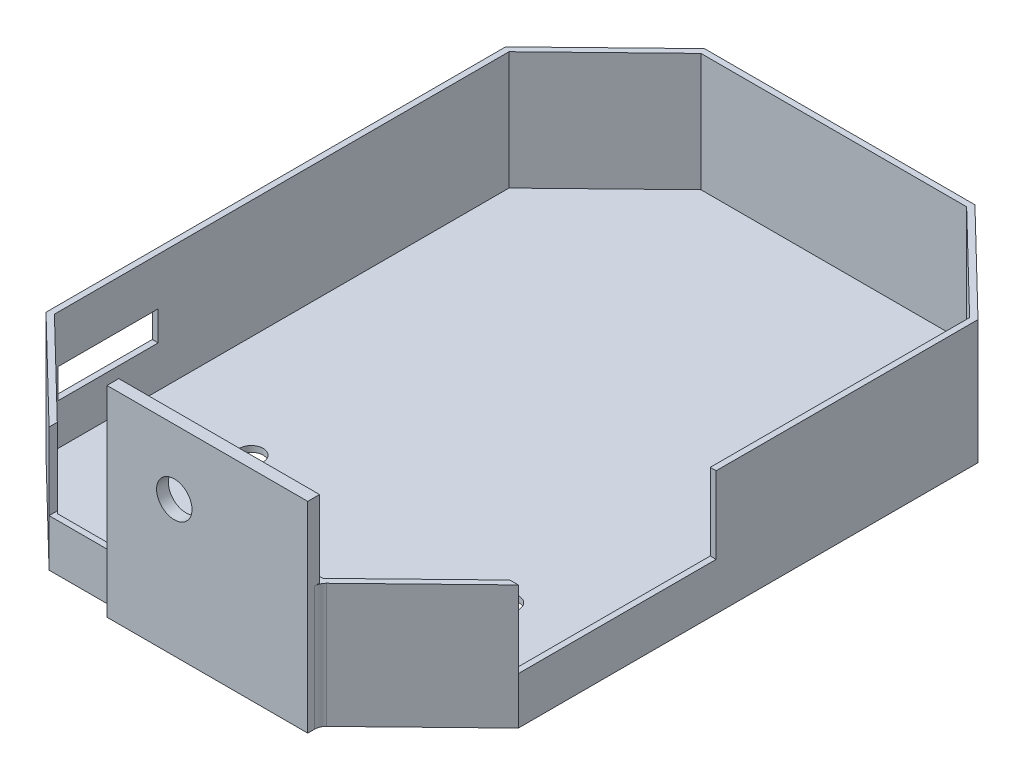
SolidWorks part; units mm, degrees
ref_plane "Alzado" through (0, 0, 0) normal (0, 0, 1) x (1, 0, 0)
ref_plane "Planta" through (0, 0, 0) normal (0, 1, 0) x (1, 0, 0)
ref_plane "Vista lateral" through (0, 0, 0) normal (1, 0, 0) x (0, 0, -1)
sketch "Croquis1" plane through (0, 0, 0) normal (0, 1, 0) x (1, 0, 0)
  line L0 (0, 0) -> (78, 0)
  line L1 (78, 0) -> (78, 109)
  line L2 (78, 109) -> (0, 109)
  line L3 (0, 109) -> (0, 0)
  line L4 (39, 109) -> (39, 0) construction
  line L5 (61.5, 109) -> (78, 93)
  line L6 (0, 54.5) -> (78, 54.5) construction
  line L7 (16.5, 109) -> (0, 93)
  line L8 (61.5, 0) -> (78, 16)
  line L9 (16.5, 0) -> (0, 16)
  dimension "D1" = 78
  dimension "D2" = 109
  dimension "D3" = 22.5
  dimension "D4" = 38.5
extrude "Saliente-Extruir1" add sketch "Croquis1" along normal blind 20 contours L9 L0 L8 L1 L5 L2 L7 L3 region at (39, 0, -54.5)
shell "Vaciado1" thickness 1 removed face at (39, 20, -54.5) outward yes
sketch "Croquis2" plane through (0, 0, 1) normal (0, 0, 1) x (1, 0, 0)
  line L0 (16.0948, 14.5) -> (61.9052, 14.5) construction
  line L1 (61.9052, 20) -> (61.9052, -1) construction
  line L2 (16.0948, 20) -> (16.0948, -1) construction
  line L3 (16.0948, -1) -> (61.9052, -1) construction
  line L4 (16.0948, 7) -> (61.9052, 7) construction
  line L5 (16.0948, 7) -> (54.0948, 7)
  line L6 (54.0948, 7) -> (54.0948, 20)
  line L7 (16.0948, 20) -> (61.9052, 20) construction
  line L8 (54.0948, 20) -> (16.0948, 20)
  line L9 (16.0948, 20) -> (16.0948, 7)
  line M4 (61.9052, 20) -> (16.0948, 20)
  line M5 (16.0948, 20) -> (16.0948, -1)
  dimension "D1" = 15.5
  dimension "D3" = 8
  dimension "D4" = 38
extrude "Cortar-Extruir1" cut sketch "Croquis2" against normal up to next contours L5 L6 M4 M5
sketch "Croquis3" plane through (79, 0, 0) normal (1, 0, 0) x (0, 0, -1)
  line L0 (49.0767, 20) -> (49.0767, 7)
  line L4 (15.5767, 20) -> (93.4233, 20) construction
  line L5 (15.5767, -1) -> (93.4233, -1) construction
  line L6 (15.5767, 20) -> (15.5767, -1) construction
  line L7 (49.0767, 20) -> (15.5767, 20)
  line L8 (15.5767, 20) -> (15.5767, 7)
  line L10 (15.5767, 7) -> (49.0767, 7)
  dimension "D1" = 33.5
  dimension "D2" = 8
extrude "Cortar-Extruir2" cut sketch "Croquis3" against normal up to next
sketch "Croquis4" plane through (-1, 0, 0) normal (-1, 0, 0) x (0, 0, 1)
  line L0 (-16.5767, 7) -> (-33.5767, 7)
  line L1 (-15.5767, 20) -> (-15.5767, -1) construction
  line L3 (-93.4233, -1) -> (-15.5767, -1) construction
  line L4 (-16.5767, 12) -> (-16.5767, 7)
  line L6 (-33.5767, 12) -> (-33.5767, 7)
  line L7 (-16.5767, 12) -> (-33.5767, 12)
  dimension "D1" = 8
  dimension "D2" = 1
  dimension "D3" = 17
  dimension "D4" = 5
extrude "Cortar-Extruir3" cut sketch "Croquis4" against normal up to next
sketch "Croquis6" plane through (0, -1, 0) normal (0, -1, 0) x (1, 0, 0)
  line L1 (79, -15.5767) -> (79, -93.4233) construction
  line L2 (-1, -93.4233) -> (-1, -15.5767) construction
  line L3 (79, -70) -> (-1, -70) construction
  line L4 (61.9052, -110) -> (16.0948, -110) construction
  text T0 "<b>BIOCRUCES BIZKAIA</b>" font "Century Gothic" height 5.5
  dimension "D1" = 40
extrude "Cortar-Extruir5" cut sketch "Croquis6" against normal blind 0.35
sketch "Croquis7" plane through (0, 0, 1) normal (0, 0, 1) x (1, 0, 0)
  line L0 (61.9052, 33) -> (27.9052, 33)
  line L1 (61.9052, -1) -> (61.9052, 33)
  line L2 (27.9052, 33) -> (27.9052, -1)
  line L3 (27.9052, -1) -> (61.9052, -1)
  line L5 (16.0948, -1) -> (61.9052, -1) construction
  point P0 (27.2079, -1)
  dimension "D1" = 34
  dimension "34" = 34
extrude "Saliente-Extruir2" add sketch "Croquis7" along normal blind 2
fillet "Redondeo1" radius 2 2 edges at (61.9052, 9.5, 1) (27.9052, 3, 1)
sketch "Croquis8" plane through (0, 0, 3) normal (0, 0, 1) x (1, 0, 0)
  line L0 (27.9052, 22) -> (61.9052, 22) construction
  line L1 (27.9052, 33) -> (27.9052, 7) construction
  line L2 (61.9052, -1) -> (61.9052, 33) construction
  line L3 (27.9052, -1) -> (61.9052, -1) construction
  line L4 (16.0948, -1) -> (62.5129, -1) construction
  line L5 (39.3039, -1) -> (39.3039, 33) construction
  line L6 (61.9052, 33) -> (27.9052, 33) construction
  circle A0 centre (39.3039, 22) radius 3
  point P18 (0, 0)
  dimension "D3" = 6
  dimension "D1" = 23
extrude "Cortar-Extruir6" cut sketch "Croquis8" against normal blind 2
sketch "Croquis9" plane through (0, 0, 0) normal (0, 1, 0) x (1, 0, 0)
  line L0 (0, 32) -> (78, 32) construction
  line L1 (0, 109) -> (0, 0) construction
  line L2 (78, 0) -> (78, 109) construction
  line L3 (61.9052, -3) -> (27.9052, -3) construction
  line L4 (39, 109) -> (39, 0) construction
  circle A0 centre (60.65, 32) radius 2
  circle A1 centre (17.35, 32) radius 2
  dimension "D2" = 4
  dimension "D3" = 4
  dimension "D1" = 35
  dimension "D4" = 43.3
  dimension "D5" = 21.65
extrude "Cortar-Extruir7" cut sketch "Croquis9" against normal blind 2
